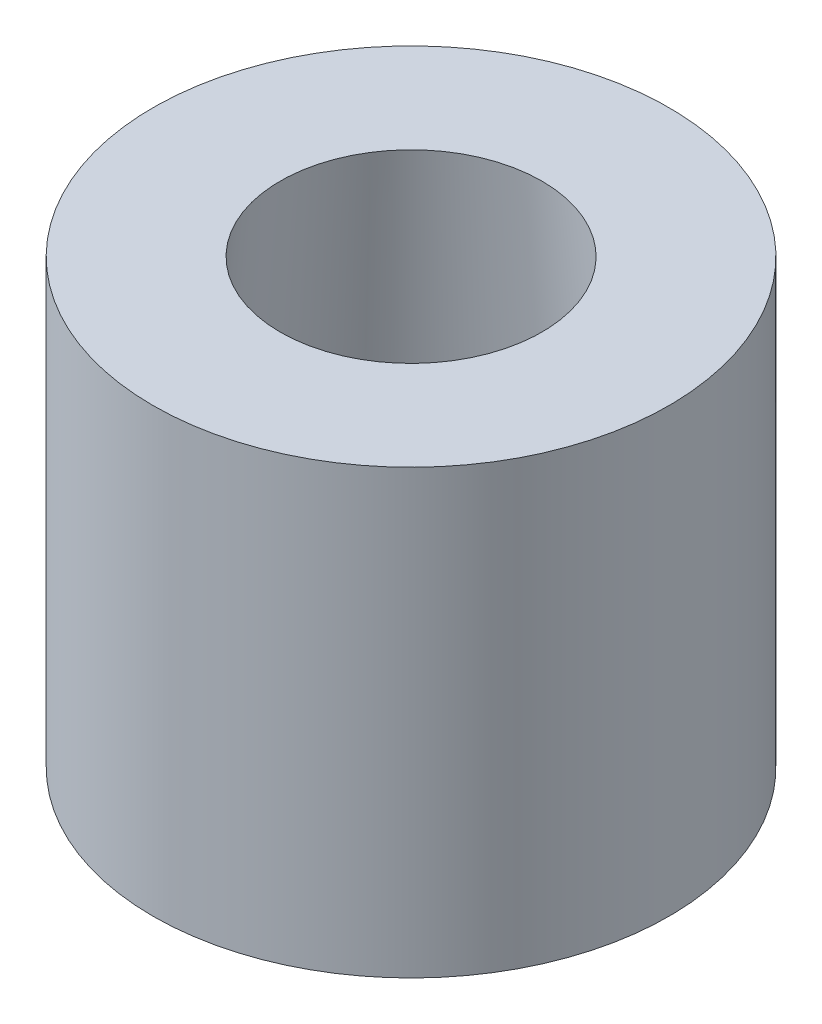
SolidWorks part; units mm, degrees
ref_plane "Front Plane" through (0, 0, 0) normal (0, 0, 1) x (1, 0, 0)
ref_plane "Top Plane" through (0, 0, 0) normal (0, 1, 0) x (1, 0, 0)
ref_plane "Right Plane" through (0, 0, 0) normal (1, 0, 0) x (0, 0, -1)
sketch "Sketch2" plane through (0, 0, 0) normal (0, 1, 0) x (1, 0, 0)
  circle A0 centre (0, 0) radius 17.5
extrude "Boss-Extrude2" add sketch "Sketch2" along normal blind 30
sketch "Sketch3" plane through (0, 0, 0) normal (0, -1, 0) x (1, 0, 0)
  circle A0 centre (0, 0) radius 11.5
extrude "Cut-Extrude1" cut sketch "Sketch3" against normal blind 30 draft 5
sketch "Sketch4" plane through (0, 0, 0) normal (0, -1, 0) x (1, 0, 0)
  circle A0 centre (0, 0) radius 12
  circle A1 centre (0, 0) radius 15.5
  dimension "D1" = 24
  dimension "D2" = 31
extrude "Cut-Extrude2" cut sketch "Sketch4" against normal blind 5
